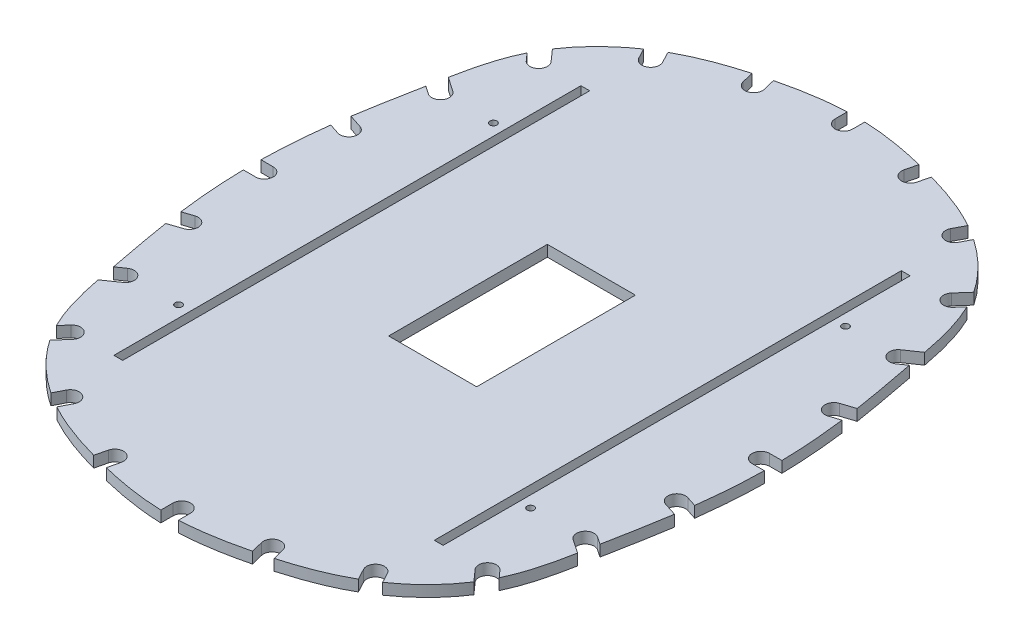
SolidWorks part; units mm, degrees
ref_plane "Front Plane" through (0, 0, 0) normal (0, 0, 1) x (1, 0, 0)
ref_plane "Top Plane" through (0, 0, 0) normal (0, 1, 0) x (1, 0, 0)
ref_plane "Right Plane" through (0, 0, 0) normal (1, 0, 0) x (0, 0, -1)
sketch "MainControlPoints" plane through (0, 0, 0) normal (0, 1, 0) x (1, 0, 0)
  line L1 (0, 188.5) -> (0, 0) construction
  line L2 (-44.5, 181.8105) -> (44.5, 181.8105) construction
  line L9 (-141, 0) -> (141, 0) construction
  line L10 (-86.25, 165.0195) -> (86.25, 165.0195) construction
  line L11 (-117.5, 132.6399) -> (117.5, 132.6399) construction
  line L12 (-130, 89.4108) -> (130, 89.4108) construction
  line L13 (-137.75, 45.0832) -> (137.75, 45.0832) construction
  spline S0 degree 3 poles (-44.8235, 182.8439) (0, 191.3281) (44.8235, 182.8439) (87.706, 168.1591) (121.8523, 134.6364) (129.8847, 89.1344) (138.6218, 45.2258) (142.1917, 0) (138.6218, -45.2258) (129.8847, -89.1344) (121.8523, -134.6364) (87.706, -168.1591) (44.8235, -182.8439) (0, -191.3281) (-44.8235, -182.8439) (-87.706, -168.1591) (-121.8523, -134.6364) (-129.8847, -89.1344) (-138.6218, -45.2258) (-142.1917, 0) (-138.6218, 45.2258) (-129.8847, 89.1344) (-121.8523, 134.6364) (-87.706, 168.1591) (-44.8235, 182.8439) (0, 191.3281) (44.8235, 182.8439) knots -0.124907 -0.083272 -0.041636 0 0.041636 0.083272 0.124907 0.166543 0.208179 0.25 0.291821 0.333457 0.375093 0.416728 0.458364 0.5 0.541636 0.583272 0.624907 0.666543 0.708179 0.75 0.791821 0.833457 0.875093 0.916728 0.958364 1 1.041636 1.083272 1.124907 only from (0, 188.5) to (0, 188.5)
  point P4 (0, 181.8105)
  point P7 (0, 0)
  point P8 (141, 0)
  point P9 (-141, 0)
  point P11 (44.5, 181.8105)
  point P14 (86.25, 165.0195)
  point P15 (0, 165.0195)
  point P16 (117.5, 132.6399)
  point P17 (130, 89.4108)
  point P18 (-44.5, 181.8105)
  point P19 (-86.25, 165.0195)
  point P20 (-117.5, 132.6399)
  point P23 (0, 132.6399)
  point P24 (137.75, 45.0832)
  point P25 (-130, 89.4108)
  point P26 (-137.75, 45.0832)
  point P27 (0, 188.5)
  point P30 (0, 89.4108)
  point P33 (0, 45.0832)
  point P34 (137.75, -45.0832)
  point P35 (130, -89.4108)
  point P36 (117.5, -132.6399)
  point P37 (86.25, -165.0195)
  point P38 (44.5, -181.8105)
  point P39 (0, -188.5)
  point P40 (-44.5, -181.8105)
  point P41 (-86.25, -165.0195)
  point P42 (-117.5, -132.6399)
  point P43 (-130, -89.4108)
  point P44 (-137.75, -45.0832)
  dimension "D3" = 282
  dimension "D2" = 188.5
  dimension "D5" = 45
  dimension "D6" = 45
  dimension "D1" = 89
  dimension "D4" = 172.5
  dimension "D7" = 45
  dimension "D8" = 235
  dimension "D9" = 45
  dimension "D10" = 260
  dimension "D11" = 45
  dimension "D12" = 275.5
ref_axis "Axis1" through (0, 0, -188.5) along (0, 1, 0)
ref_axis "Axis2" through (44.5, 0, -181.8105) along (0, 1, 0)
ref_axis "Axis3" through (86.25, 0, -165.0195) along (0, 1, 0)
ref_axis "Axis4" through (117.5, 0, -132.6399) along (0, 1, 0)
ref_axis "Axis5" through (130, 0, -89.4108) along (0, 1, 0)
ref_axis "Axis6" through (137.75, 0, -45.0832) along (0, 1, 0)
ref_axis "Axis7" through (141, 0, 0) along (0, 1, 0)
ref_axis "Axis8" through (137.75, 0, 45.0832) along (0, 1, 0)
ref_axis "Axis9" through (130, 0, 89.4108) along (0, 1, 0)
ref_axis "Axis10" through (117.5, 0, 132.6399) along (0, 1, 0)
ref_axis "Axis11" through (86.25, 0, 165.0195) along (0, 1, 0)
ref_axis "Axis12" through (44.5, 0, 181.8105) along (0, 1, 0)
ref_axis "Axis13" through (0, 0, 188.5) along (0, 1, 0)
ref_axis "Axis14" through (-44.5, 0, 181.8105) along (0, 1, 0)
ref_axis "Axis15" through (-86.25, 0, 165.0195) along (0, 1, 0)
ref_axis "Axis16" through (-117.5, 0, 132.6399) along (0, 1, 0)
ref_axis "Axis17" through (-130, 0, 89.4108) along (0, 1, 0)
ref_axis "Axis18" through (-137.75, 0, 45.0832) along (0, 1, 0)
ref_axis "Axis19" through (-141, 0, 0) along (0, 1, 0)
ref_axis "Axis20" through (-137.75, 0, -45.0832) along (0, 1, 0)
ref_axis "Axis21" through (-130, 0, -89.4108) along (0, 1, 0)
ref_axis "Axis22" through (-117.5, 0, -132.6399) along (0, 1, 0)
ref_axis "Axis23" through (-86.25, 0, -165.0195) along (0, 1, 0)
ref_axis "Axis24" through (-44.5, 0, -181.8105) along (0, 1, 0)
sketch "Sketch3" plane through (0, 0, 0) normal (0, 1, 0) x (1, 0, 0)
  spline S2 degree 3 poles (44.8235, 182.8439) (0, 191.3281) (-44.8235, 182.8439) (-87.706, 168.1591) (-121.8523, 134.6364) (-129.8847, 89.1344) (-138.6218, 45.2258) (-142.1917, 0) (-138.6218, -45.2258) (-129.8847, -89.1344) (-121.8523, -134.6364) (-87.706, -168.1591) (-44.8235, -182.8439) (0, -191.3281) (44.8235, -182.8439) (87.706, -168.1591) (121.8523, -134.6364) (129.8847, -89.1344) (138.6218, -45.2258) (142.1917, 0) (138.6218, 45.2258) (129.8847, 89.1344) (121.8523, 134.6364) (87.706, 168.1591) (44.8235, 182.8439) (0, 191.3281) (-44.8235, 182.8439) knots -0.124907 -0.083272 -0.041636 0 0.041636 0.083272 0.124907 0.166543 0.208179 0.25 0.291821 0.333457 0.375093 0.416728 0.458364 0.5 0.541636 0.583272 0.624907 0.666543 0.708179 0.75 0.791821 0.833457 0.875093 0.916728 0.958364 1 1.041636 1.083272 1.124907 only from (0, 188.5) to (0, 188.5)
  spline S3 degree 3 poles (44.8235, 182.8439) (0, 191.3281) (-44.8235, 182.8439) (-87.706, 168.1591) (-121.8523, 134.6364) (-129.8847, 89.1344) (-138.6218, 45.2258) (-142.1917, 0) (-138.6218, -45.2258) (-129.8847, -89.1344) (-121.8523, -134.6364) (-87.706, -168.1591) (-44.8235, -182.8439) (0, -191.3281) (44.8235, -182.8439) (87.706, -168.1591) (121.8523, -134.6364) (129.8847, -89.1344) (138.6218, -45.2258) (142.1917, 0) (138.6218, 45.2258) (129.8847, 89.1344) (121.8523, 134.6364) (87.706, 168.1591) (44.8235, 182.8439) (0, 191.3281) (-44.8235, 182.8439) knots -0.124907 -0.083272 -0.041636 0 0.041636 0.083272 0.124907 0.166543 0.208179 0.25 0.291821 0.333457 0.375093 0.416728 0.458364 0.5 0.541636 0.583272 0.624907 0.666543 0.708179 0.75 0.791821 0.833457 0.875093 0.916728 0.958364 1 1.041636 1.083272 1.124907 only from (0, 188.5) to (0, 188.5)
  dimension "D1" = 0
extrude "MainBody" add sketch "Sketch3" along normal blind 6.35
sketch "Sketch13" plane through (0, 6.35, 0) normal (0, 1, 0) x (1, 0, 0)
  spline S2 degree 3 poles (-0.0923, -195.5) (5.9061, -195.5) (11.7392, -195.085) (23.2981, -193.6453) (29.0237, -192.6199) (37.5559, -190.7615) (40.3905, -190.0886) (46.0447, -188.657) (48.8649, -187.9023) (53.0829, -186.6998) (54.4867, -186.2866) (57.2893, -185.4316) (58.6882, -184.9896) (62.8604, -183.6197) (65.6138, -182.6462) (73.7714, -179.5048) (79.0728, -177.1157) (86.7462, -172.933) (89.2575, -171.4385) (92.9463, -169.029) (94.1653, -168.1965) (96.5575, -166.4889) (97.7326, -165.6128) (101.1944, -162.9177) (103.4182, -161.032) (107.6923, -157.0772) (109.7427, -155.0081) (112.678, -151.7562) (113.633, -150.6474) (115.0284, -148.9451) (115.4873, -148.3711) (116.3925, -147.2097) (116.8393, -146.6213) (119.0306, -143.6582) (120.6466, -141.2209) (123.5916, -136.206) (124.9153, -133.6259) (127.2923, -128.3337) (128.3485, -125.623) (129.7723, -121.4785) (130.2202, -120.084) (131.0691, -117.272) (131.4694, -115.8571) (132.6042, -111.6095) (133.2755, -108.7656) (134.5145, -103.0626) (135.0819, -100.2036) (136.1775, -94.48) (136.707, -91.6156) (138.3251, -83.0265) (139.4215, -77.303) (141.5293, -65.8438) (142.5403, -60.108) (143.9035, -51.4821) (144.3323, -48.6031) (145.1247, -42.8358) (145.4885, -39.9475) (147.1362, -25.4811) (147.9101, -13.8294) (148.003, -0.6092) (148.0024, 0.8623) (147.9792, 3.8019) (147.9568, 5.2701) (147.8578, 9.6699) (147.7498, 12.5969) (147.3068, 21.3604) (146.8533, 27.1792) (145.6651, 38.7754) (144.9284, 44.5524) (143.2126, 56.0705) (142.2389, 61.8124) (140.1775, 73.2794) (139.0901, 79.0044) (137.4645, 87.5929) (136.9262, 90.4562) (135.8531, 96.1835) (135.3122, 99.0464) (133.5786, 107.6189) (132.2779, 113.3124) (130.1353, 120.3529) (129.6824, 121.7514) (128.7233, 124.5187) (128.2169, 125.8886) (126.6073, 129.9525) (125.4138, 132.6004) (122.7385, 137.7496) (121.2544, 140.2496) (118.8215, 143.8945) (117.9761, 145.0919) (116.2177, 147.4523) (115.3033, 148.6168) (112.4942, 152.0199) (110.5242, 154.1827) (106.4077, 158.3162) (104.2612, 160.2869) (99.8013, 164.0465) (97.4878, 165.8355) (93.8939, 168.384) (92.6724, 169.2128) (90.2027, 170.8151) (88.9554, 171.5879) (82.6598, 175.3171) (77.4348, 177.8708) (66.7035, 182.3362) (61.1969, 184.2476) (54.1978, 186.3725) (52.791, 186.7846) (49.9736, 187.5842) (48.5634, 187.9716) (44.3294, 189.1029) (41.5021, 189.818) (33.0032, 191.8167) (27.3144, 192.953) (15.8708, 194.6608) (10.1162, 195.2328) (1.4182, 195.5241) (-1.4925, 195.5238) (-7.3372, 195.3237) (-10.2708, 195.1267) (-14.6866, 194.6996) (-16.1609, 194.5352) (-19.0943, 194.1679) (-20.556, 193.9647) (-24.9277, 193.3015) (-27.824, 192.7881) (-36.4681, 191.071) (-42.1715, 189.6926) (-53.5026, 186.6371) (-59.1262, 184.9441) (-66.0624, 182.4605) (-67.445, 181.9454) (-70.1997, 180.8739) (-71.5737, 180.3168) (-75.6639, 178.5832) (-78.3432, 177.3468) (-83.5935, 174.6901) (-86.1644, 173.2698) (-91.1858, 170.2243) (-93.6357, 168.5985) (-97.2169, 166.0005) (-98.395, 165.108) (-100.7189, 163.2682) (-101.8655, 162.32) (-105.2234, 159.4186) (-107.3637, 157.4004) (-111.4418, 153.191) (-113.3796, 150.9998) (-117.0378, 146.4319) (-118.7583, 144.0551) (-121.1568, 140.3344) (-121.9259, 139.0681) (-123.0304, 137.1268) (-123.3898, 136.4736) (-124.087, 135.1618) (-124.4255, 134.5022) (-126.0692, 131.1868) (-127.2294, 128.4785) (-130.3408, 120.2205) (-131.9223, 114.5371) (-134.5909, 102.9918) (-135.6643, 97.1921) (-137.8355, 85.5987) (-138.9477, 79.8043) (-141.1029, 68.2094) (-142.1451, 62.4088) (-143.5618, 53.6948) (-144.0097, 50.788) (-144.8419, 44.9686) (-145.2255, 42.056) (-146.97, 27.4776) (-147.815, 15.7657) (-148.0521, -1.8942) (-147.9538, -7.7967) (-147.4225, -19.6316) (-146.9909, -25.5639) (-146.1143, -34.4827) (-145.7838, -37.4592) (-145.0527, -43.3941) (-144.6515, -46.3556) (-143.3516, -55.2244) (-142.36, -61.1163) (-140.253, -72.8796) (-139.1381, -78.7512) (-137.4708, -87.5593) (-136.9189, -90.496) (-135.8181, -96.3698) (-135.2627, -99.3053) (-133.4794, -108.0788) (-132.1352, -113.8842) (-129.4893, -122.4151) (-128.5024, -125.2292) (-126.8117, -129.3912) (-126.2131, -130.7686) (-125.2553, -132.818) (-124.9263, -133.498) (-124.2516, -134.843) (-123.9056, -135.5092) (-122.1306, -138.8075) (-120.5688, -141.343) (-117.1925, -146.2303) (-115.378, -148.582) (-111.5149, -153.1153) (-109.4647, -155.2983) (-105.1449, -159.494) (-102.9036, -161.4797) (-95.9543, -167.1259) (-91.0211, -170.4758) (-84.4967, -174.1698) (-83.1716, -174.8856) (-80.5028, -176.2632) (-79.1594, -176.925) (-75.1047, -178.8358) (-72.3686, -180.0105) (-64.0786, -183.2871) (-58.4429, -185.1422) (-49.8888, -187.6214) (-47.0211, -188.3984) (-41.2605, -189.8765) (-38.3664, -190.5739) (-32.5429, -191.862) (-29.6099, -192.4531) (-23.735, -193.4975) (-20.7901, -193.9515) (-14.8831, -194.699) (-11.9208, -194.9924) (-7.4624, -195.2928) (-5.9738, -195.3696) (-3.7367, -195.4473) (-2.6172, -195.4768) (-1.3092, -195.4942) (-0.6548, -195.4985) (-0.3742, -195.4995) (-0.1871, -195.4999) (-0.0923, -195.5) (5.9061, -195.5) (11.7392, -195.085) knots -0.000244 -0.000244 0 0 0.015625 0.015625 0.03125 0.03125 0.039063 0.039063 0.046875 0.046875 0.050781 0.050781 0.054688 0.054688 0.0625 0.0625 0.078125 0.078125 0.085938 0.085938 0.089844 0.089844 0.09375 0.09375 0.101563 0.101563 0.109375 0.109375 0.113281 0.113281 0.115234 0.115234 0.117188 0.117188 0.125 0.125 0.132813 0.132813 0.140625 0.140625 0.144531 0.144531 0.148438 0.148438 0.15625 0.15625 0.164063 0.164063 0.171875 0.171875 0.1875 0.1875 0.203125 0.203125 0.210938 0.210938 0.21875 0.21875 0.25 0.25 0.253906 0.253906 0.257813 0.257813 0.265625 0.265625 0.28125 0.28125 0.296875 0.296875 0.3125 0.3125 0.328125 0.328125 0.335938 0.335938 0.34375 0.34375 0.359375 0.359375 0.363281 0.363281 0.367188 0.367188 0.375 0.375 0.382813 0.382813 0.386719 0.386719 0.390625 0.390625 0.398438 0.398438 0.40625 0.40625 0.414063 0.414063 0.417969 0.417969 0.421875 0.421875 0.4375 0.4375 0.453125 0.453125 0.457031 0.457031 0.460938 0.460938 0.46875 0.46875 0.484375 0.484375 0.5 0.5 0.507813 0.507813 0.515625 0.515625 0.519531 0.519531 0.523438 0.523438 0.53125 0.53125 0.546875 0.546875 0.5625 0.5625 0.566406 0.566406 0.570313 0.570313 0.578125 0.578125 0.585938 0.585938 0.59375 0.59375 0.597656 0.597656 0.601563 0.601563 0.609375 0.609375 0.617188 0.617188 0.625 0.625 0.628906 0.628906 0.630859 0.630859 0.632813 0.632813 0.640625 0.640625 0.65625 0.65625 0.671875 0.671875 0.6875 0.6875 0.703125 0.703125 0.710937 0.710937 0.71875 0.71875 0.75 0.75 0.765625 0.765625 0.78125 0.78125 0.789062 0.789062 0.796875 0.796875 0.8125 0.8125 0.828125 0.828125 0.835937 0.835937 0.84375 0.84375 0.859375 0.859375 0.867187 0.867187 0.871094 0.871094 0.873047 0.873047 0.875 0.875 0.882812 0.882812 0.890625 0.890625 0.898437 0.898437 0.90625 0.90625 0.921875 0.921875 0.925781 0.925781 0.929687 0.929687 0.9375 0.9375 0.953125 0.953125 0.960937 0.960937 0.96875 0.96875 0.976562 0.976562 0.984375 0.984375 0.992188 0.992188 0.996094 0.996094 0.998047 0.999023 0.999512 0.999756 0.999756 1 1 1.015625 1.015625 1.03125 only from (0, -195.5) to (0, -195.5)
  spline S3 degree 3 poles (-0.0923, -195.5) (5.9061, -195.5) (11.7392, -195.085) (23.2981, -193.6453) (29.0237, -192.6199) (37.5559, -190.7615) (40.3905, -190.0886) (46.0447, -188.657) (48.8649, -187.9023) (53.0829, -186.6998) (54.4867, -186.2866) (57.2893, -185.4316) (58.6882, -184.9896) (62.8604, -183.6197) (65.6138, -182.6462) (73.7714, -179.5048) (79.0728, -177.1157) (86.7462, -172.933) (89.2575, -171.4385) (92.9463, -169.029) (94.1653, -168.1965) (96.5575, -166.4889) (97.7326, -165.6128) (101.1944, -162.9177) (103.4182, -161.032) (107.6923, -157.0772) (109.7427, -155.0081) (112.678, -151.7562) (113.633, -150.6474) (115.0284, -148.9451) (115.4873, -148.3711) (116.3925, -147.2097) (116.8393, -146.6213) (119.0306, -143.6582) (120.6466, -141.2209) (123.5916, -136.206) (124.9153, -133.6259) (127.2923, -128.3337) (128.3485, -125.623) (129.7723, -121.4785) (130.2202, -120.084) (131.0691, -117.272) (131.4694, -115.8571) (132.6042, -111.6095) (133.2755, -108.7656) (134.5145, -103.0626) (135.0819, -100.2036) (136.1775, -94.48) (136.707, -91.6156) (138.3251, -83.0265) (139.4215, -77.303) (141.5293, -65.8438) (142.5403, -60.108) (143.9035, -51.4821) (144.3323, -48.6031) (145.1247, -42.8358) (145.4885, -39.9475) (147.1362, -25.4811) (147.9101, -13.8294) (148.003, -0.6092) (148.0024, 0.8623) (147.9792, 3.8019) (147.9568, 5.2701) (147.8578, 9.6699) (147.7498, 12.5969) (147.3068, 21.3604) (146.8533, 27.1792) (145.6651, 38.7754) (144.9284, 44.5524) (143.2126, 56.0705) (142.2389, 61.8124) (140.1775, 73.2794) (139.0901, 79.0044) (137.4645, 87.5929) (136.9262, 90.4562) (135.8531, 96.1835) (135.3122, 99.0464) (133.5786, 107.6189) (132.2779, 113.3124) (130.1353, 120.3529) (129.6824, 121.7514) (128.7233, 124.5187) (128.2169, 125.8886) (126.6073, 129.9525) (125.4138, 132.6004) (122.7385, 137.7496) (121.2544, 140.2496) (118.8215, 143.8945) (117.9761, 145.0919) (116.2177, 147.4523) (115.3033, 148.6168) (112.4942, 152.0199) (110.5242, 154.1827) (106.4077, 158.3162) (104.2612, 160.2869) (99.8013, 164.0465) (97.4878, 165.8355) (93.8939, 168.384) (92.6724, 169.2128) (90.2027, 170.8151) (88.9554, 171.5879) (82.6598, 175.3171) (77.4348, 177.8708) (66.7035, 182.3362) (61.1969, 184.2476) (54.1978, 186.3725) (52.791, 186.7846) (49.9736, 187.5842) (48.5634, 187.9716) (44.3294, 189.1029) (41.5021, 189.818) (33.0032, 191.8167) (27.3144, 192.953) (15.8708, 194.6608) (10.1162, 195.2328) (1.4182, 195.5241) (-1.4925, 195.5238) (-7.3372, 195.3237) (-10.2708, 195.1267) (-14.6866, 194.6996) (-16.1609, 194.5352) (-19.0943, 194.1679) (-20.556, 193.9647) (-24.9277, 193.3015) (-27.824, 192.7881) (-36.4681, 191.071) (-42.1715, 189.6926) (-53.5026, 186.6371) (-59.1262, 184.9441) (-66.0624, 182.4605) (-67.445, 181.9454) (-70.1997, 180.8739) (-71.5737, 180.3168) (-75.6639, 178.5832) (-78.3432, 177.3468) (-83.5935, 174.6901) (-86.1644, 173.2698) (-91.1858, 170.2243) (-93.6357, 168.5985) (-97.2169, 166.0005) (-98.395, 165.108) (-100.7189, 163.2682) (-101.8655, 162.32) (-105.2234, 159.4186) (-107.3637, 157.4004) (-111.4418, 153.191) (-113.3796, 150.9998) (-117.0378, 146.4319) (-118.7583, 144.0551) (-121.1568, 140.3344) (-121.9259, 139.0681) (-123.0304, 137.1268) (-123.3898, 136.4736) (-124.087, 135.1618) (-124.4255, 134.5022) (-126.0692, 131.1868) (-127.2294, 128.4785) (-130.3408, 120.2205) (-131.9223, 114.5371) (-134.5909, 102.9918) (-135.6643, 97.1921) (-137.8355, 85.5987) (-138.9477, 79.8043) (-141.1029, 68.2094) (-142.1451, 62.4088) (-143.5618, 53.6948) (-144.0097, 50.788) (-144.8419, 44.9686) (-145.2255, 42.056) (-146.97, 27.4776) (-147.815, 15.7657) (-148.0521, -1.8942) (-147.9538, -7.7967) (-147.4225, -19.6316) (-146.9909, -25.5639) (-146.1143, -34.4827) (-145.7838, -37.4592) (-145.0527, -43.3941) (-144.6515, -46.3556) (-143.3516, -55.2244) (-142.36, -61.1163) (-140.253, -72.8796) (-139.1381, -78.7512) (-137.4708, -87.5593) (-136.9189, -90.496) (-135.8181, -96.3698) (-135.2627, -99.3053) (-133.4794, -108.0788) (-132.1352, -113.8842) (-129.4893, -122.4151) (-128.5024, -125.2292) (-126.8117, -129.3912) (-126.2131, -130.7686) (-125.2553, -132.818) (-124.9263, -133.498) (-124.2516, -134.843) (-123.9056, -135.5092) (-122.1306, -138.8075) (-120.5688, -141.343) (-117.1925, -146.2303) (-115.378, -148.582) (-111.5149, -153.1153) (-109.4647, -155.2983) (-105.1449, -159.494) (-102.9036, -161.4797) (-95.9543, -167.1259) (-91.0211, -170.4758) (-84.4967, -174.1698) (-83.1716, -174.8856) (-80.5028, -176.2632) (-79.1594, -176.925) (-75.1047, -178.8358) (-72.3686, -180.0105) (-64.0786, -183.2871) (-58.4429, -185.1422) (-49.8888, -187.6214) (-47.0211, -188.3984) (-41.2605, -189.8765) (-38.3664, -190.5739) (-32.5429, -191.862) (-29.6099, -192.4531) (-23.735, -193.4975) (-20.7901, -193.9515) (-14.8831, -194.699) (-11.9208, -194.9924) (-7.4624, -195.2928) (-5.9738, -195.3696) (-3.7367, -195.4473) (-2.6172, -195.4768) (-1.3092, -195.4942) (-0.6548, -195.4985) (-0.3742, -195.4995) (-0.1871, -195.4999) (-0.0923, -195.5) (5.9061, -195.5) (11.7392, -195.085) knots -0.000244 -0.000244 0 0 0.015625 0.015625 0.03125 0.03125 0.039063 0.039063 0.046875 0.046875 0.050781 0.050781 0.054688 0.054688 0.0625 0.0625 0.078125 0.078125 0.085938 0.085938 0.089844 0.089844 0.09375 0.09375 0.101563 0.101563 0.109375 0.109375 0.113281 0.113281 0.115234 0.115234 0.117188 0.117188 0.125 0.125 0.132813 0.132813 0.140625 0.140625 0.144531 0.144531 0.148438 0.148438 0.15625 0.15625 0.164063 0.164063 0.171875 0.171875 0.1875 0.1875 0.203125 0.203125 0.210938 0.210938 0.21875 0.21875 0.25 0.25 0.253906 0.253906 0.257813 0.257813 0.265625 0.265625 0.28125 0.28125 0.296875 0.296875 0.3125 0.3125 0.328125 0.328125 0.335938 0.335938 0.34375 0.34375 0.359375 0.359375 0.363281 0.363281 0.367188 0.367188 0.375 0.375 0.382813 0.382813 0.386719 0.386719 0.390625 0.390625 0.398438 0.398438 0.40625 0.40625 0.414063 0.414063 0.417969 0.417969 0.421875 0.421875 0.4375 0.4375 0.453125 0.453125 0.457031 0.457031 0.460938 0.460938 0.46875 0.46875 0.484375 0.484375 0.5 0.5 0.507813 0.507813 0.515625 0.515625 0.519531 0.519531 0.523438 0.523438 0.53125 0.53125 0.546875 0.546875 0.5625 0.5625 0.566406 0.566406 0.570313 0.570313 0.578125 0.578125 0.585938 0.585938 0.59375 0.59375 0.597656 0.597656 0.601563 0.601563 0.609375 0.609375 0.617188 0.617188 0.625 0.625 0.628906 0.628906 0.630859 0.630859 0.632813 0.632813 0.640625 0.640625 0.65625 0.65625 0.671875 0.671875 0.6875 0.6875 0.703125 0.703125 0.710937 0.710937 0.71875 0.71875 0.75 0.75 0.765625 0.765625 0.78125 0.78125 0.789062 0.789062 0.796875 0.796875 0.8125 0.8125 0.828125 0.828125 0.835937 0.835937 0.84375 0.84375 0.859375 0.859375 0.867187 0.867187 0.871094 0.871094 0.873047 0.873047 0.875 0.875 0.882812 0.882812 0.890625 0.890625 0.898437 0.898437 0.90625 0.90625 0.921875 0.921875 0.925781 0.925781 0.929687 0.929687 0.9375 0.9375 0.953125 0.953125 0.960937 0.960937 0.96875 0.96875 0.976562 0.976562 0.984375 0.984375 0.992188 0.992188 0.996094 0.996094 0.998047 0.999023 0.999512 0.999756 0.999756 1 1 1.015625 1.015625 1.03125 only from (0, -195.5) to (0, -195.5)
  dimension "D1" = 7
extrude "Extrude2Lip" add sketch "Sketch13" against normal up to surface (6.35 mm away)
sketch "Sketch14" plane through (0, 6.35, 0) normal (0, 1, 0) x (1, 0, 0)
  line L0 (-5, 188.5) -> (-5, 199.1798)
  line L1 (-5, 199.1798) -> (5, 199.1798)
  line L2 (5, 199.1798) -> (5, 188.5)
  line L9 (0, 188.5) -> (0, 199.1798) construction
  line L13 (-5, 188.5) -> (5, 188.5) construction
  line L20 (39.6434, 182.9992) -> (42.1824, 193.3728)
  line L21 (42.1824, 193.3728) -> (51.8957, 190.9953)
  line L22 (0, 0) -> (44.5, 181.8105) construction
  line L23 (0, 0) -> (86.25, 165.0195) construction
  line L24 (0, 0) -> (117.5, 132.6399) construction
  line L25 (0, 0) -> (130, 89.4108) construction
  line L26 (0, 0) -> (137.75, 45.0832) construction
  line L27 (0, 0) -> (141, 0.3435) construction
  line L28 (0, 0) -> (0, 188.5) construction
  line L29 (51.8957, 190.9953) -> (49.3566, 180.6217)
  line L30 (44.5, 181.8105) -> (47.039, 192.1841) construction
  line L31 (39.6434, 182.9992) -> (49.3566, 180.6217) construction
  line L32 (81.8188, 167.3355) -> (86.7658, 176.8005)
  line L33 (86.7658, 176.8005) -> (95.6283, 172.1684)
  line L34 (95.6283, 172.1684) -> (90.6812, 162.7034)
  line L35 (86.25, 165.0195) -> (91.197, 174.4844) construction
  line L36 (81.8188, 167.3355) -> (90.6812, 162.7034) construction
  line L37 (113.7573, 135.9554) -> (125.8891, 149.6503)
  line L38 (125.8891, 149.6503) -> (133.3744, 143.0193)
  line L39 (133.3744, 143.0193) -> (121.2427, 129.3244)
  line L40 (117.5, 132.6399) -> (129.6317, 146.3348) construction
  line L41 (113.7573, 135.9554) -> (121.2427, 129.3244) construction
  line L42 (127.1666, 93.5305) -> (142.2527, 103.9064)
  line L43 (142.2527, 103.9064) -> (147.9195, 95.667)
  line L44 (147.9195, 95.667) -> (132.8334, 85.2912)
  line L45 (130, 89.4108) -> (145.0861, 99.7867) construction
  line L46 (127.1666, 93.5305) -> (132.8334, 85.2912) construction
  line L47 (136.1948, 49.8352) -> (153.5963, 55.5304)
  line L48 (153.5963, 55.5304) -> (156.7067, 46.0265)
  line L49 (156.7067, 46.0265) -> (139.3052, 40.3312)
  line L50 (137.75, 45.0832) -> (155.1515, 50.7784) construction
  line L51 (136.1948, 49.8352) -> (139.3052, 40.3312) construction
  line L52 (140.9878, 5.3435) -> (159.2975, 5.3881)
  line L53 (159.2975, 5.3881) -> (159.3219, -4.6119)
  line L54 (159.3219, -4.6119) -> (141.0122, -4.6565)
  line L55 (141, 0.3435) -> (159.3097, 0.3881) construction
  line L56 (140.9878, 5.3435) -> (141.0122, -4.6565) construction
  line L57 (-140.9878, 5.3435) -> (-141.0122, -4.6565) construction
  line L58 (-141, 0.3435) -> (-159.3097, 0.3881) construction
  line L59 (-136.1948, 49.8352) -> (-139.3052, 40.3312) construction
  line L60 (-137.75, 45.0832) -> (-155.1515, 50.7784) construction
  line L61 (-127.1666, 93.5305) -> (-132.8334, 85.2912) construction
  line L62 (-130, 89.4108) -> (-145.0861, 99.7867) construction
  line L63 (-113.7573, 135.9554) -> (-121.2427, 129.3244) construction
  line L64 (-117.5, 132.6399) -> (-129.6317, 146.3348) construction
  line L65 (-81.8188, 167.3355) -> (-90.6812, 162.7034) construction
  line L66 (-86.25, 165.0195) -> (-91.197, 174.4844) construction
  line L67 (-39.6434, 182.9992) -> (-49.3566, 180.6217) construction
  line L68 (-44.5, 181.8105) -> (-47.039, 192.1841) construction
  line L69 (-159.3219, -4.6119) -> (-141.0122, -4.6565)
  line L70 (-159.2975, 5.3881) -> (-159.3219, -4.6119)
  line L71 (-140.9878, 5.3435) -> (-159.2975, 5.3881)
  line L72 (-156.7067, 46.0265) -> (-139.3052, 40.3312)
  line L73 (-153.5963, 55.5304) -> (-156.7067, 46.0265)
  line L74 (-136.1948, 49.8352) -> (-153.5963, 55.5304)
  line L75 (-147.9195, 95.667) -> (-132.8334, 85.2912)
  line L76 (-142.2527, 103.9064) -> (-147.9195, 95.667)
  line L77 (-127.1666, 93.5305) -> (-142.2527, 103.9064)
  line L78 (-133.3744, 143.0193) -> (-121.2427, 129.3244)
  line L79 (-125.8891, 149.6503) -> (-133.3744, 143.0193)
  line L80 (-113.7573, 135.9554) -> (-125.8891, 149.6503)
  line L81 (-95.6283, 172.1684) -> (-90.6812, 162.7034)
  line L82 (-86.7658, 176.8005) -> (-95.6283, 172.1684)
  line L83 (-81.8188, 167.3355) -> (-86.7658, 176.8005)
  line L84 (-51.8957, 190.9953) -> (-49.3566, 180.6217)
  line L85 (-42.1824, 193.3728) -> (-51.8957, 190.9953)
  line L86 (-39.6434, 182.9992) -> (-42.1824, 193.3728)
  line L87 (-43.6136, -182.0251) -> (-46.1021, -192.411) construction
  line L88 (-38.7512, -183.1902) -> (-48.476, -180.8601) construction
  line L89 (-85.4449, -165.4378) -> (-90.3457, -174.9267) construction
  line L90 (-81.0024, -167.7322) -> (-89.8874, -163.1433) construction
  line L91 (-116.8523, -133.2108) -> (-128.9172, -146.9647) construction
  line L92 (-113.0935, -136.508) -> (-120.6111, -129.9136) construction
  line L93 (-129.5628, -90.0432) -> (-144.5981, -100.4924) construction
  line L94 (-126.7093, -94.149) -> (-132.4163, -85.9374) construction
  line L95 (-137.5287, -45.7539) -> (-154.9022, -51.5338) construction
  line L96 (-135.9503, -50.4982) -> (-139.1071, -41.0095) construction
  line L97 (136.436, -49.171) -> (139.5001, -39.652) construction
  line L98 (137.968, -44.4115) -> (155.3971, -50.0219) construction
  line L99 (127.6208, -92.9098) -> (133.2474, -84.6429) construction
  line L100 (130.4341, -88.7763) -> (145.5706, -99.0786) construction
  line L101 (114.4184, -135.3995) -> (121.8714, -128.7321) construction
  line L102 (118.1449, -132.0658) -> (130.3432, -145.7014) construction
  line L103 (82.6331, -166.9349) -> (91.4729, -162.2596) construction
  line L104 (87.053, -164.5972) -> (92.0461, -174.038) construction
  line L105 (40.5346, -182.8038) -> (50.2361, -180.3791) construction
  line L106 (45.3853, -181.5915) -> (47.9749, -191.9526) construction
  line L107 (-4.0815, -188.5221) -> (5.9184, -188.4734) construction
  line L108 (0.9185, -188.4978) -> (0.9705, -199.1775) construction
  line L109 (-38.7512, -183.1902) -> (-41.2397, -193.576)
  line L110 (-41.2397, -193.576) -> (-50.9644, -191.2459)
  line L111 (-50.9644, -191.2459) -> (-48.476, -180.8601)
  line L112 (-81.0024, -167.7322) -> (-85.9033, -177.2212)
  line L113 (-85.9033, -177.2212) -> (-94.7882, -172.6323)
  line L114 (-94.7882, -172.6323) -> (-89.8874, -163.1433)
  line L115 (-113.0935, -136.508) -> (-125.1584, -150.2619)
  line L116 (-125.1584, -150.2619) -> (-132.676, -143.6675)
  line L117 (-132.676, -143.6675) -> (-120.6111, -129.9136)
  line L118 (-126.7093, -94.149) -> (-141.7447, -104.5983)
  line L119 (-141.7447, -104.5983) -> (-147.4516, -96.3866)
  line L120 (-147.4516, -96.3866) -> (-132.4163, -85.9374)
  line L121 (-135.9503, -50.4982) -> (-153.3239, -56.2781)
  line L122 (-153.3239, -56.2781) -> (-156.4806, -46.7895)
  line L123 (-156.4806, -46.7895) -> (-139.1071, -41.0095)
  line L124 (156.9292, -45.2624) -> (139.5001, -39.652)
  line L125 (153.865, -54.7813) -> (156.9292, -45.2624)
  line L126 (136.436, -49.171) -> (153.865, -54.7813)
  line L127 (148.3839, -94.9451) -> (133.2474, -84.6429)
  line L128 (142.7573, -103.212) -> (148.3839, -94.9451)
  line L129 (127.6208, -92.9098) -> (142.7573, -103.212)
  line L130 (134.0697, -142.3677) -> (121.8714, -128.7321)
  line L131 (126.6167, -149.0351) -> (134.0697, -142.3677)
  line L132 (114.4184, -135.3995) -> (126.6167, -149.0351)
  line L133 (96.466, -171.7004) -> (91.4729, -162.2596)
  line L134 (87.6262, -176.3756) -> (96.466, -171.7004)
  line L135 (82.6331, -166.9349) -> (87.6262, -176.3756)
  line L136 (52.8257, -190.7402) -> (50.2361, -180.3791)
  line L137 (43.1241, -193.1649) -> (52.8257, -190.7402)
  line L138 (40.5346, -182.8038) -> (43.1241, -193.1649)
  line L139 (5.9704, -199.1531) -> (5.9184, -188.4734)
  line L140 (-4.0294, -199.2018) -> (5.9704, -199.1531)
  line L141 (-4.0815, -188.5221) -> (-4.0294, -199.2018)
  arc A0 (-5, 188.5) -> (5, 188.5) centre (0, 188.5) ccw
  arc A1 (39.6434, 182.9992) -> (49.3566, 180.6217) centre (44.5, 181.8105) ccw
  arc A2 (81.8188, 167.3355) -> (90.6812, 162.7034) centre (86.25, 165.0195) ccw
  arc A3 (113.7573, 135.9554) -> (121.2427, 129.3244) centre (117.5, 132.6399) ccw
  arc A4 (127.1666, 93.5305) -> (132.8334, 85.2912) centre (130, 89.4108) ccw
  arc A5 (136.1948, 49.8352) -> (139.3052, 40.3312) centre (137.75, 45.0832) ccw
  arc A6 (140.9878, 5.3435) -> (141.0122, -4.6565) centre (141, 0.3435) ccw
  arc A7 (-140.9878, 5.3435) -> (-141.0122, -4.6565) centre (-141, 0.3435) cw
  arc A8 (-136.1948, 49.8352) -> (-139.3052, 40.3312) centre (-137.75, 45.0832) cw
  arc A9 (-127.1666, 93.5305) -> (-132.8334, 85.2912) centre (-130, 89.4108) cw
  arc A10 (-113.7573, 135.9554) -> (-121.2427, 129.3244) centre (-117.5, 132.6399) cw
  arc A11 (-81.8188, 167.3355) -> (-90.6812, 162.7034) centre (-86.25, 165.0195) cw
  arc A12 (-39.6434, 182.9992) -> (-49.3566, 180.6217) centre (-44.5, 181.8105) cw
  arc A13 (-38.7512, -183.1902) -> (-48.476, -180.8601) centre (-43.6136, -182.0251) ccw
  arc A14 (-81.0024, -167.7322) -> (-89.8874, -163.1433) centre (-85.4449, -165.4378) ccw
  arc A15 (-113.0935, -136.508) -> (-120.6111, -129.9136) centre (-116.8523, -133.2108) ccw
  arc A16 (-126.7093, -94.149) -> (-132.4163, -85.9374) centre (-129.5628, -90.0432) ccw
  arc A17 (-135.9503, -50.4982) -> (-139.1071, -41.0095) centre (-137.5287, -45.7539) ccw
  arc A18 (136.436, -49.171) -> (139.5001, -39.652) centre (137.968, -44.4115) cw
  arc A19 (127.6208, -92.9098) -> (133.2474, -84.6429) centre (130.4341, -88.7763) cw
  arc A20 (114.4184, -135.3995) -> (121.8714, -128.7321) centre (118.1449, -132.0658) cw
  arc A21 (82.6331, -166.9349) -> (91.4729, -162.2596) centre (87.053, -164.5972) cw
  arc A22 (40.5346, -182.8038) -> (50.2361, -180.3791) centre (45.3853, -181.5915) cw
  arc A23 (-4.0815, -188.5221) -> (5.9184, -188.4734) centre (0.9185, -188.4978) cw
  point P16 (44.5, 181.8105)
  dimension "D1" = 5
  dimension "D4" = 10
extrude "Slots" cut sketch "Sketch14" against normal up to next
ref_plane "MajorAxisPlane" through (0, 0, 0) normal (-1, 0, 0) x (0, 0, 1)
ref_plane "MinorAxisPlane" through (0, 0, 0) normal (0, 0, 1) x (1, 0, 0)
sketch "Sketch15" plane through (0, 6.35, 0) normal (0, 1, 0) x (1, 0, 0)
  line L3 (0, 164.9718) -> (0, -164.9718) construction
  line L4 (-164.9718, 0) -> (164.9718, 0) construction
  line L5 (-130, 89.4108) -> (130, 89.4108) construction
  line L6 (0, 188.5) -> (0, 0) construction
  circle A0 centre (-100, 89.4108) radius 2
  circle A1 centre (100, 89.4108) radius 2
  circle A2 centre (100, -89.4108) radius 2
  circle A3 centre (-100, -89.4108) radius 2
  dimension "D1" = 4
  dimension "D2" = 100
extrude "LiftCableAccess" cut sketch "Sketch15" against normal up to next
sketch "Sketch16" plane through (0, 6.35, 0) normal (0, 1, 0) x (1, 0, 0)
  line L0 (-141, 0) -> (141, 0) construction
  line L1 (-93.5, -132.6399) -> (-88.5, -132.6399)
  line L2 (-93.5, -132.6399) -> (-93.5, 132.6399)
  line L3 (-93.5, 132.6399) -> (-88.5, 132.6399)
  line L4 (-88.5, -132.6399) -> (-88.5, 132.6399)
  line L5 (-93.5, -132.6399) -> (-88.5, 132.6399) construction
  line L6 (-93.5, 132.6399) -> (-88.5, -132.6399) construction
  line L7 (-117.5, 132.6399) -> (117.5, 132.6399) construction
  line L9 (0, 164.9718) -> (0, -164.9718) construction
  line L10 (93.5, 132.6399) -> (88.5, -132.6399) construction
  line L11 (93.5, -132.6399) -> (88.5, 132.6399) construction
  line L12 (88.5, -132.6399) -> (88.5, 132.6399)
  line L13 (93.5, 132.6399) -> (88.5, 132.6399)
  line L14 (93.5, -132.6399) -> (93.5, 132.6399)
  line L15 (93.5, -132.6399) -> (88.5, -132.6399)
  point P0 (-91, 0)
  point P16 (91, 0)
  dimension "D1" = 50
  dimension "D2" = 5
extrude "CushionSupport" cut sketch "Sketch16" against normal up to next
sketch "Sketch17" plane through (0, 6.35, 0) normal (0, 1, 0) x (1, 0, 0)
  line L0 (-137.75, 45.0832) -> (137.75, 45.0832) construction
  line L1 (-25, -45.0832) -> (25, -45.0832)
  line L2 (-25, -45.0832) -> (-25, 45.0832)
  line L3 (-25, 45.0832) -> (25, 45.0832)
  line L4 (25, -45.0832) -> (25, 45.0832)
  line L5 (-25, -45.0832) -> (25, 45.0832) construction
  line L6 (-25, 45.0832) -> (25, -45.0832) construction
  point P0 (0, 0)
  dimension "D1" = 50
extrude "Handle" cut sketch "Sketch17" against normal up to next
equation "\"MajorAxis\"= 377mm"
equation "\"MinorAxis\"= 282mm"
equation "\"MajorDiagonal\"= 353mm"
equation "\"SlotSpacing\"= 45mm"
equation "\"SlotRadius\"=5"
equation "\"D3@MainControlPoints\" = \"MinorAxis\""
equation "\"D2@MainControlPoints\" = \"MajorAxis\" / 2"
equation "\"D5@MainControlPoints\" = \"SlotSpacing\""
equation "\"D7@MainControlPoints\" = \"SlotSpacing\""
equation "\"D9@MainControlPoints\" = \"SlotSpacing\""
equation "\"D11@MainControlPoints\" = \"SlotSpacing\""
equation "\"D1@Sketch14\"=\"SlotRadius\""
equation "\"D4@Sketch14\"=\"SlotRadius\" * 2"
equation "\"Pt2LipEdge\"=7"
equation "\"D1@Sketch13\"=\"Pt2LipEdge\""
